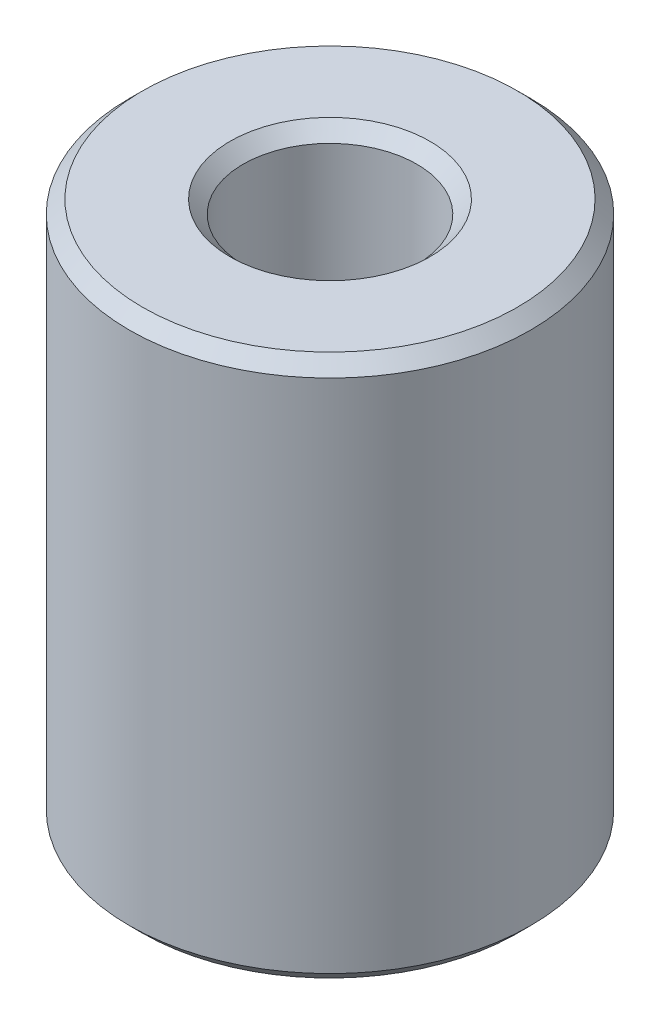
SolidWorks part; units mm, degrees
ref_plane "Front Plane" through (0, 0, 0) normal (0, 0, 1) x (1, 0, 0)
ref_plane "Top Plane" through (0, 0, 0) normal (0, 1, 0) x (1, 0, 0)
ref_plane "Right Plane" through (0, 0, 0) normal (1, 0, 0) x (0, 0, -1)
sketch "Sketch1" plane through (0, 0, 0) normal (0, 1, 0) x (1, 0, 0)
  circle A0 centre (0, 0) radius 12.5
  dimension "SLEEVE_OD" = 25
extrude "Boss-Extrude1" add sketch "Sketch1" along normal blind 33.7737
sketch "Sketch2" plane through (0, 0, 0) normal (0, 1, 0) x (1, 0, 0)
  circle A0 centre (0, 0) radius 5.4113
  dimension "BORE_D" = 10.8226
extrude "Cut-Extrude1" cut sketch "Sketch2" along normal through all
chamfer "Chamfer1" distance 0.8217 angle 45 4 edges at (0, 33.7737, 5.4113) (0, 0, 5.4113) (0, 0, 12.5) (0, 33.7737, 12.5)
